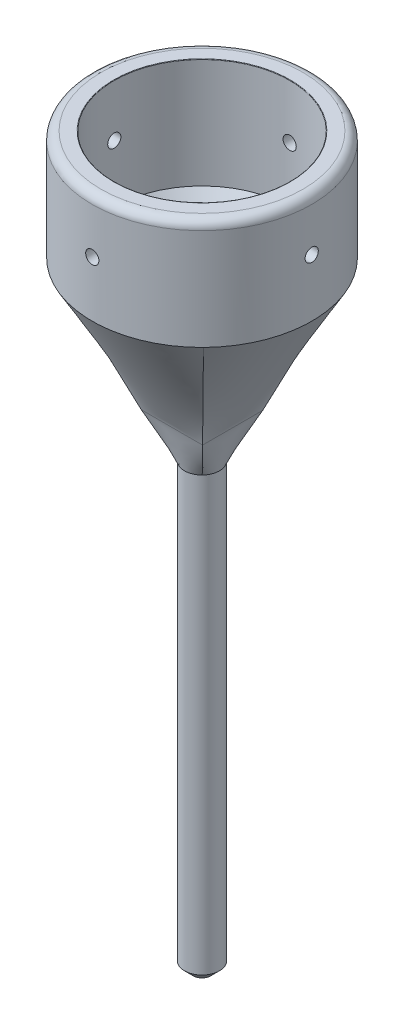
SolidWorks part; units mm, degrees
ref_plane "Front Plane" through (0, 0, 0) normal (0, 0, 1) x (1, 0, 0)
ref_plane "Top Plane" through (0, 0, 0) normal (0, 1, 0) x (1, 0, 0)
ref_plane "Right Plane" through (0, 0, 0) normal (1, 0, 0) x (0, 0, -1)
sketch "Sketch1" plane through (0, 0, 0) normal (0, 1, 0) x (1, 0, 0)
  line L0 (0, 0) -> (0, -2.9878) construction
  circle A0 centre (0, 0) radius 3.98
extrude "Boss-Extrude1" add sketch "Sketch1" along normal blind 85
ref_plane "Plane1" through (0, 85, 0) normal (0, 1, 0) x (1, 0, 0)
sketch "Sketch2" plane through (0, 85, 0) normal (0, 1, 0) x (1, 0, 0)
  circle A0 centre (0, 0) radius 3.98
extrude "Boss-Extrude2" add sketch "Sketch2" along normal blind 15.5
ref_plane "Plane3" through (0, 100.5, 0) normal (0, 1, 0) x (1, 0, 0)
sketch "Sketch4" plane through (0, 100.5, 0) normal (0, 1, 0) x (1, 0, 0)
  circle A0 centre (0, 0) radius 3.98
ref_plane "Plane4" through (0, 110.5, 0) normal (0, 1, 0) x (1, 0, 0)
sketch "Sketch5" plane through (0, 110.5, 0) normal (0, 1, 0) x (1, 0, 0)
  line L1 (-6.972, 6.8413) -> (6.972, 6.8413)
  line L2 (-6.972, 6.8413) -> (-6.972, -6.8413)
  line L3 (-6.972, -6.8413) -> (6.972, -6.8413)
  line L4 (6.972, 6.8413) -> (6.972, -6.8413)
  line L5 (-6.972, 6.8413) -> (6.972, -6.8413) construction
  line L6 (-6.972, -6.8413) -> (6.972, 6.8413) construction
  point P0 (0, 0)
loft "Loft1" add profiles "Sketch5", "Sketch4" connector at (6.972, 110.5, 6.8413) connector at (0, 100.5, 3.98)
ref_plane "Plane5" through (0, 140.5, 0) normal (0, 1, 0) x (1, 0, 0)
sketch "Sketch6" plane through (0, 140.5, 0) normal (0, 1, 0) x (1, 0, 0)
  circle A1 centre (0, 0) radius 25
sketch "Sketch7" plane through (0, 110.5, 0) normal (0, 1, 0) x (1, 0, 0)
  line L1 (-6.972, 6.8413) -> (6.972, 6.8413)
  line L2 (-6.972, 6.8413) -> (-6.972, -6.8413)
  line L3 (-6.972, -6.8413) -> (6.972, -6.8413)
  line L4 (6.972, 6.8413) -> (6.972, -6.8413)
  line L5 (-6.972, 6.8413) -> (6.972, -6.8413) construction
  line L6 (-6.972, -6.8413) -> (6.972, 6.8413) construction
loft "Loft2" add profiles "Sketch6", "Sketch7" connector at (0, 140.5, 25) connector at (6.972, 110.5, -6.8413)
sketch "Sketch8" plane through (0, 140.5, 0) normal (0, 1, 0) x (1, 0, 0)
  circle A0 centre (0, 0) radius 20
extrude "Cut-Extrude2" cut sketch "Sketch8" against normal blind 15.5 draft 36 contours A0
sketch "Sketch9" plane through (0, 140.5, 0) normal (0, 1, 0) x (1, 0, 0)
  circle A0 centre (0, 0) radius 20
  circle A1 centre (0, 0) radius 25
extrude "Boss-Extrude3" add sketch "Sketch9" along normal blind 25
sketch "Sketch11" plane through (0, 0, 0) normal (1, 0, 0) x (0, 0, -1)
  circle A0 centre (0, 153.5833) radius 1.5
sketch "Sketch12" plane through (0, 0, 0) normal (0, 0, 1) x (1, 0, 0)
  circle A0 centre (0, 153.1415) radius 1.5
extrude "Cut-Extrude3" cut sketch "Sketch11" against normal blind 30 and the other way blind 30
extrude "Cut-Extrude4" cut sketch "Sketch12" against normal blind 30 and the other way blind 30
fillet "Fillet2" radius 2 1 edges at (0, 165.5, 25)
fillet "Fillet3" radius 0.1 1 edges at (0, 165.5, 20)
chamfer "Chamfer1" distance 2 angle 45 1 edges at (0, 0, 3.98)
